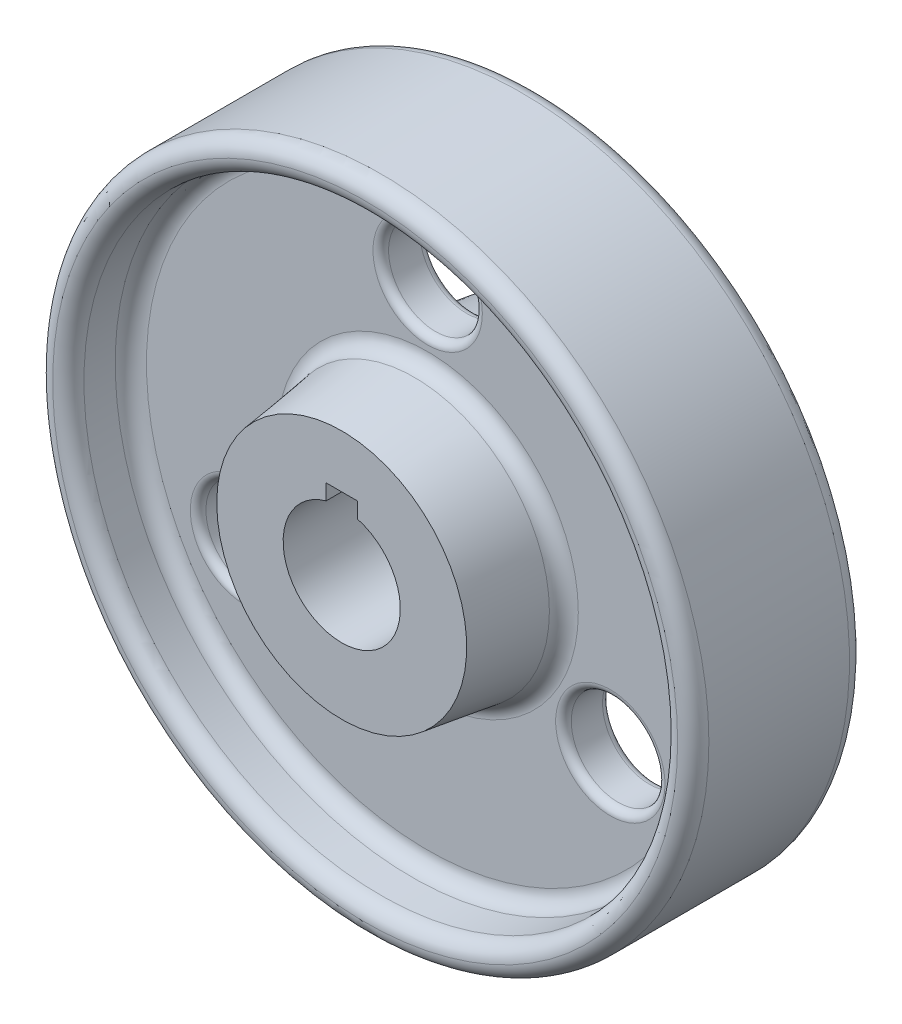
SolidWorks part; units mm, degrees
material "AISI 1020"
ref_plane "Plane1" through (0, 0, 0) normal (0, 0, 1) x (1, 0, 0)
ref_plane "Plane2" through (0, 0, 0) normal (0, 1, 0) x (1, 0, 0)
ref_plane "Plane3" through (0, 0, 0) normal (1, 0, 0) x (0, 0, -1)
sketch "Esquisse1" plane through (0, 0, 0) normal (1, 0, 0) x (0, 0, -1)
  line L0 (-60, 0) -> (60, 0) construction
  line L1 (-22.225, 11.9062) -> (22.225, 11.9062)
  line L2 (22.225, 11.9062) -> (22.225, 25.4)
  line L3 (-22.225, 11.9062) -> (-22.225, 25.4)
  line L4 (-22.225, 25.4) -> (-4.7625, 27.8542)
  line L5 (-4.7625, 27.8542) -> (-4.7625, 60.325)
  line L6 (4.7625, 60.325) -> (4.7625, 27.8542)
  line L7 (4.7625, 27.8542) -> (22.225, 25.4)
  line L8 (4.7625, 60.325) -> (17.4625, 60.325)
  line L9 (17.4625, 60.325) -> (17.4625, 66.675)
  line L10 (17.4625, 66.675) -> (-17.4625, 66.675)
  line L11 (-17.4625, 66.675) -> (-17.4625, 60.325)
  line L12 (-17.4625, 60.325) -> (-4.7625, 60.325)
  line L13 (-22.225, 25.4) -> (0.8006, 25.4) construction
  dimension "D1" = 44.45
  dimension "D2" = 34.925
  dimension "D3" = 9.525
  dimension "D4" = 50.8
  dimension "D5" = 23.8125
  dimension "D6" = 133.35
  dimension "D7" = 120.65
  dimension "D8" = 22.225
  dimension "D9" = 8
revolve "Base-Révolution" add sketch "Esquisse1" angle 360 about L0
hole_wizard "Diamètre du perçage 3/4 (0.75)2" positions "Esquisse3" profile "Esquisse2" hole size "3/4" standard "Ansi Inch" end condition through all
sketch "Esquisse3" plane through (0, 0, 4.7625) normal (0, 0, 1) x (1, 0, 0)
  circle A0 centre (0, 0) radius 66.675 construction
  point P0 (0, 42.8625)
  dimension "D1" = 42.8625
sketch "Esquisse2" plane through (0, 42.8625, 4.7625) normal (1, 0, 0) x (0, -1, 0)
  line L0 (0, 0) -> (0, 26.9875)
  line L1 (0, 26.9875) -> (9.525, 26.9875)
  line L2 (9.525, 26.9875) -> (9.525, 0)
  line L5 (9.525, 0) -> (0, 0)
  line L11 (0, -6.35) -> (0, 107.95) construction
  dimension "Diamètre du perçage jusqu'au prochain" = 19.05
  dimension "Profondeur du perçage jusqu'au prochain" = 26.9875
pattern_circular "Répétition circulaire1" count 3 every 120 about axis through (0, 0, 0) along (0, 0, 1) of "Diamètre du perçage 3/4 (0.75)2"
fillet "Congé1" radius 1.5875 6 edges at (-9.525, 42.8625, -4.7625) (9.525, 42.8625, 4.7625) (-46.645, -21.4313, -4.7625) (-27.595, -21.4313, 4.7625) (27.595, -21.4312, -4.7625) (46.645, -21.4312, 4.7625)
fillet "Congé2" radius 3.175 6 edges at (-60.325, 0, -4.7625) (-60.325, 0, -17.4625) (-60.325, 0, 17.4625) (-60.325, 0, 4.7625) (-27.8542, 0, 4.7625) (-27.8542, 0, -4.7625)
fillet "Congé3" radius 3.175 2 edges at (-66.675, 0, -17.4625) (-66.675, 0, 17.4625)
sketch "Esquisse4" plane through (0, 0, 22.225) normal (0, 0, 1) x (1, 0, 0)
  line L1 (-3.175, 14.6501) -> (3.175, 14.6501)
  line L2 (-3.175, 14.6501) -> (-3.175, 11.4751)
  line L3 (-3.175, 11.4751) -> (3.175, 11.4751)
  line L4 (3.175, 14.6501) -> (3.175, 11.4751)
  circle A0 centre (0, 0) radius 11.9062 construction
  point P4 (0, 11.4751)
  dimension "D1" = 6.35
  dimension "D2" = 3.175
extrude "Enlèv. mat.-Extru.1" cut sketch "Esquisse4" against normal through all
